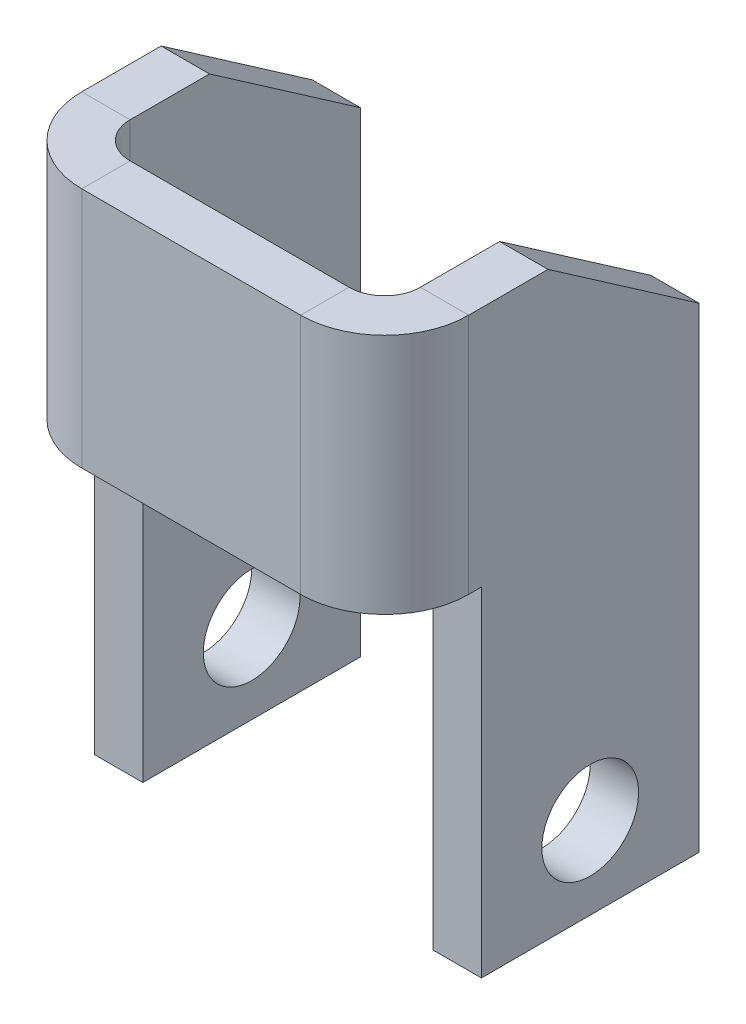
SolidWorks part; units mm, degrees
note: The reader was unsure of these and kept them because the rebuilt part matched: thickness of "Brida base1", "Brida de arista1", "Chapa metálica1", "Chapa metálica2", "Chapa metálica3", "Chapa metálica4", "Chapa metálica5"; flange length of "Brida de arista1".
ref_plane "Alzado" through (0, 0, 0) normal (0, 0, 1) x (1, 0, 0)
ref_plane "Planta" through (0, 0, 0) normal (0, 1, 0) x (1, 0, 0)
ref_plane "Vista lateral" through (0, 0, 0) normal (1, 0, 0) x (0, 0, -1)
sketch "Croquis1" plane through (0, 0, 0) normal (0, 0, 1) x (1, 0, 0)
  line L1 (-4, -10.5) -> (4, -10.5)
  line L2 (-4, -10.5) -> (-4, 10.5)
  line L3 (-4, 10.5) -> (4, 10.5)
  line L4 (4, -10.5) -> (4, 10.5)
  line L5 (-4, -10.5) -> (4, 10.5) construction
  line L6 (-4, 10.5) -> (4, -10.5) construction
  point P0 (0, 0)
  dimension "D1" = 8
  dimension "D2" = 21
base flange "Brida base1" sketch "Croquis1" thickness 1 reverse thickness direction no parameters "D1"=0.7366
edge flange "Brida de arista1" sketch "Croquis32" flange profiles "Croquis32", "Croquis33" flange angle 90 flange length 6.5 flange position material inside bend radius 0.7366 thickness 1 relief rectangular parameters "D6"=10, "D8"=0.5
sketch "Croquis32" plane through (-4, 0, -1) normal (-1, 0, 0) x (0, 1, 0)
  line L0 (10.5, 0) -> (-10.5, 0) construction
  line L1 (10.5, 0) -> (-10.5, 0)
  line L2 (-10.5, 0) -> (-10.5, 5.5)
  line L3 (-10.5, 5.5) -> (10.5, 5.5)
  line L4 (10.5, 5.5) -> (10.5, 0)
sketch "Croquis33" plane through (4, 0, -1) normal (1, 0, 0) x (0, -1, 0)
  line L0 (10.5, 0) -> (-10.5, 0) construction
  line L1 (10.5, 0) -> (-10.5, 0)
  line L2 (-10.5, 0) -> (-10.5, 5.5)
  line L3 (-10.5, 5.5) -> (10.5, 5.5)
  line L4 (10.5, 5.5) -> (10.5, 0)
bend "Pliegue de arista1" bend radius 0.7366 bend angle 90 parameters "D5"=1
bend "Pliegue de arista2" bend radius 0.7366 bend angle 90 parameters "D5"=2
sketch "Croquis34" plane through (4, 0, 0) normal (1, 0, 0) x (0, 0, -1)
  line L0 (6.5, -10.5) -> (6.5, 10.5) construction
  line L1 (0, 10.5) -> (2, 10.5)
  line L2 (0, 10.5) -> (0, 3.5)
  line L3 (0, 3.5) -> (2, 3.5)
  line L4 (2, 10.5) -> (2, 3.5)
  line L5 (0, 0) -> (6.5, 0) construction
  line L6 (2, -10.5) -> (2, -3.5)
  line L7 (0, -3.5) -> (2, -3.5)
  line L8 (0, -10.5) -> (0, -3.5)
  line L9 (0, -10.5) -> (2, -10.5)
  dimension "D1" = 4.5
  dimension "D2" = 7
extrude "Cortar-Extruir1" cut sketch "Croquis34" against normal blind 10 normal cut yes
sketch "Croquis35" plane through (4, 0, 0) normal (1, 0, 0) x (0, 0, -1)
  line L0 (6.5, 0) -> (1.7366, 0) construction
  line L2 (4.25, 10.5) -> (4.25, 8.8) construction
  line L3 (6.5, 10.5) -> (2, 10.5) construction
  line L4 (6.5, -10.5) -> (6.5, 10.5) construction
  line L5 (1.7366, -3.5) -> (1.7366, 3.5) construction
  line L6 (4.25, -10.5) -> (4.25, -8.8) construction
  circle A0 centre (4.25, 8.8) radius 1
  circle A1 centre (4.25, -8.8) radius 1
  dimension "D3" = 2
  dimension "D1" = 1.7
extrude "Cortar-Extruir2" cut sketch "Croquis35" against normal up to surface (8 mm away) normal cut yes up to face at (-4, 0, -3.0592)
sketch "Croquis36" plane through (4, 0, 0) normal (1, 0, 0) x (0, 0, -1)
  line L0 (0, 1.5) -> (3.3775, 1.5)
  line L1 (0, -3.5) -> (0, 3.5) construction
  line L2 (3.3775, 1.5) -> (6.5, -0.6664)
  line L3 (6.5, -10.5) -> (6.5, 10.5) construction
  line L4 (6.5, -0.6664) -> (6.5, 11.1574)
  line L5 (6.5, 11.1574) -> (0, 11.1574)
  line L6 (0, 11.1574) -> (0, 1.5)
  line L7 (1.7366, 3.5) -> (0, 3.5) construction
  dimension "D1" = 2
extrude "Cortar-Extruir3" cut sketch "Croquis36" against normal blind 10 normal cut yes
sketch "Líneas de pliegue1" [suppressed] plane through (0, 0, 0) normal (0, 1, 0) x (1, 0, 0)
sketch "Cuadro delimitador1" [suppressed] plane through (0, 0, 0) normal (0, 1, 0) x (1, 0, 0)
sheet metal parameters "Chapa metálica1" thickness 1 parameters "D1"=0.7366
flat pattern "Chapa desplegada1" [suppressed]
sketch "Líneas de pliegue2" plane through (0, 0, 0) normal (0, 1, 0) x (1, 0, 0)
sketch3d "Cuadro delimitador2" [suppressed]
  line L0 (-4, 10.5, 0) -> (-4, -10.5, 0) construction
  line L1 (4, 10.5, 0) -> (4, -10.5, 0) construction
  line L2 (-4, 10.5, 0) -> (4, 10.5, 0) construction
  line L3 (-4, -10.5, 0) -> (4, -10.5, 0) construction
sheet metal parameters "Chapa metálica2" thickness 1 parameters "D1"=0.7366, "D7"=1.5
flat pattern "Chapa desplegada1"
sketch "Líneas de pliegue2" plane through (0, 0, 0) normal (0, 0, 1) x (1, 0, 0)
  line L0 (2.931, -10.5) -> (2.931, 10.5) construction
  line L1 (-2.931, 10.5) -> (-2.931, -10.5) construction
  line L2 (2.931, -10.5) -> (2.931, 10.5) construction
  line L3 (-2.931, 10.5) -> (-2.931, -10.5) construction
sketch3d "Cuadro delimitador2" [suppressed]
  line L0 (8.3619, 10.5, 0) -> (8.3619, -10.5, 0) construction
  line L1 (-8.3619, 10.5, 0) -> (-8.3619, -10.5, 0) construction
  line L2 (8.3619, 10.5, 0) -> (-8.3619, 10.5, 0) construction
  line L3 (8.3619, -10.5, 0) -> (-8.3619, -10.5, 0) construction
bend of the flat pattern "Aplanar-<Pliegue de arista1>1"
bend of the flat pattern "Aplanar-<Pliegue de arista2>1"
sheet metal parameters "Chapa metálica3" thickness 1 parameters "D1"=0.7366, "D7"=1.5
flat pattern "Chapa desplegada1"
sketch "Líneas de pliegue2" plane through (0, 0, 0) normal (0, 0, 1) x (1, 0, 0)
  line L0 (3.2346, -3.5) -> (3.2346, 3.5) construction
  line L1 (-3.2346, 3.5) -> (-3.2346, -3.5) construction
  line L2 (3.2346, -3.5) -> (3.2346, 3.5) construction
  line L3 (-3.2346, 3.5) -> (-3.2346, -3.5) construction
sketch3d "Cuadro delimitador2" [suppressed]
  line L0 (8.9692, 10.5, 0) -> (8.9692, -10.5, 0) construction
  line L1 (-8.9692, 10.5, 0) -> (-8.9692, -10.5, 0) construction
  line L2 (8.9692, 10.5, 0) -> (-8.9692, 10.5, 0) construction
  line L3 (8.9692, -10.5, 0) -> (-8.9692, -10.5, 0) construction
bend of the flat pattern "Aplanar-<Pliegue de arista1>1"
bend of the flat pattern "Aplanar-<Pliegue de arista2>1"
sheet metal parameters "Chapa metálica4" thickness 1 parameters "D1"=0.7366, "D7"=1.5
flat pattern "Chapa desplegada1"
sketch "Líneas de pliegue2" plane through (0, 0, 0) normal (0, 0, 1) x (1, 0, 0)
  line L0 (3.2346, -3.5) -> (3.2346, 3.5) construction
  line L1 (-3.2346, 3.5) -> (-3.2346, -3.5) construction
  line L2 (3.2346, -3.5) -> (3.2346, 3.5) construction
  line L3 (-3.2346, 3.5) -> (-3.2346, -3.5) construction
sketch3d "Cuadro delimitador2" [suppressed]
  line L0 (8.9692, 10.5, 0) -> (8.9692, -10.5, 0) construction
  line L1 (-8.9692, 10.5, 0) -> (-8.9692, -10.5, 0) construction
  line L2 (8.9692, 10.5, 0) -> (-8.9692, 10.5, 0) construction
  line L3 (8.9692, -10.5, 0) -> (-8.9692, -10.5, 0) construction
bend of the flat pattern "Aplanar-<Pliegue de arista1>1"
bend of the flat pattern "Aplanar-<Pliegue de arista2>1"
sheet metal parameters "Chapa metálica5" thickness 1 parameters "D1"=0.7366, "D7"=1.5
flat pattern "Chapa desplegada1"
sketch "Líneas de pliegue2" plane through (0, 0, 0) normal (0, 0, 1) x (1, 0, 0)
  line L0 (3.2346, -3.5) -> (3.2346, 1.5) construction
  line L1 (-3.2346, 1.5) -> (-3.2346, -3.5) construction
  line L2 (3.2346, -3.5) -> (3.2346, 1.5) construction
  line L3 (-3.2346, 1.5) -> (-3.2346, -3.5) construction
sketch3d "Cuadro delimitador2" [suppressed]
  line L0 (-8.9692, -10.5, 0) -> (8.9692, -10.5, 0) construction
  line L1 (-8.9692, 1.5, 0) -> (8.9692, 1.5, 0) construction
  line L2 (-8.9692, -10.5, 0) -> (-8.9692, 1.5, 0) construction
  line L3 (8.9692, -10.5, 0) -> (8.9692, 1.5, 0) construction
bend of the flat pattern "Aplanar-<Pliegue de arista1>1"
bend of the flat pattern "Aplanar-<Pliegue de arista2>1"
